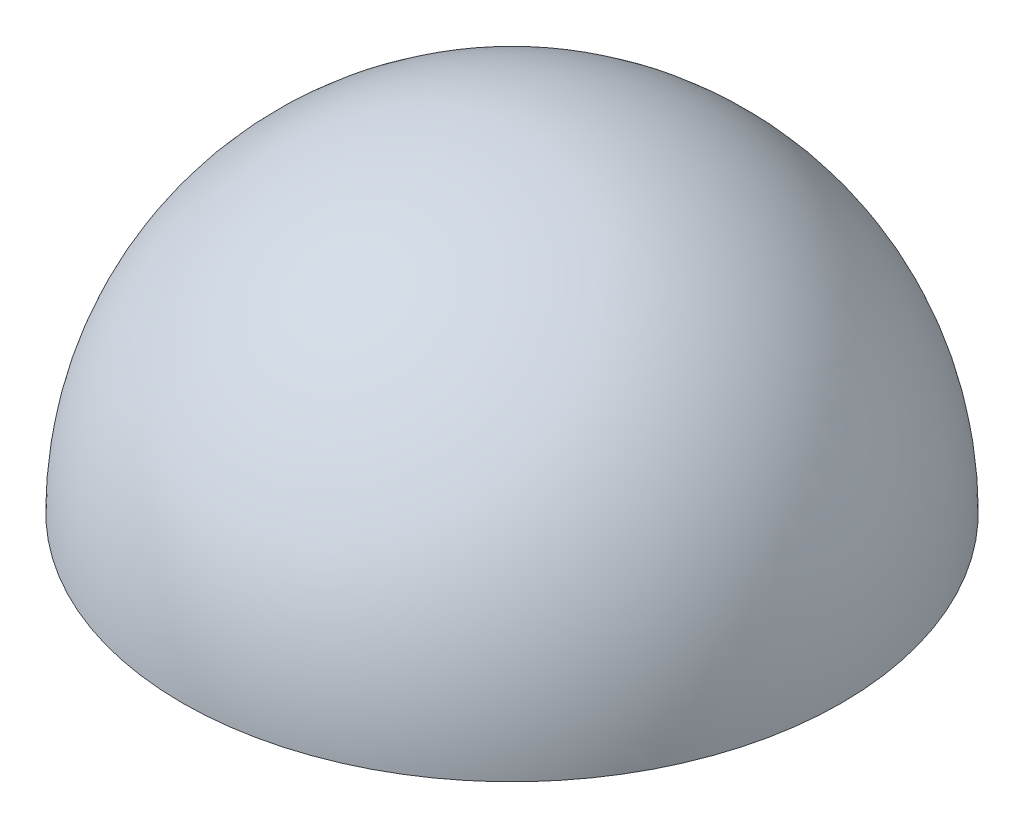
SolidWorks part; units mm, degrees
note: '?' marks a value the reader was unsure of.
material "Rubber"
ref_plane "Front Plane" through (0, 0, 0) normal (0, 0, 1) x (1, 0, 0)
ref_plane "Top Plane" through (0, 0, 0) normal (0, 1, 0) x (1, 0, 0)
ref_plane "Right Plane" through (0, 0, 0) normal (1, 0, 0) x (0, 0, -1)
sketch "Sketch1" plane through (0, 0, 0) normal (0, 0, 1) x (1, 0, 0)
  line L0 (0, 0) -> (0, 12.7)
  line L1 (-12.7, 0) -> (0, 0)
  line L2 (0, 0) -> (0, 0.0519)
  arc A0 (0, 12.7) -> (-12.7, 0) centre (0, 0) ccw
  dimension "D1" = 12.7
revolve "Revolve1" add sketch "Sketch1" angle 360 about L0
ref_axis "Axis1" through (0, 13.335, 0) along (0, -1, 0)?
ref_point "fingertip"
